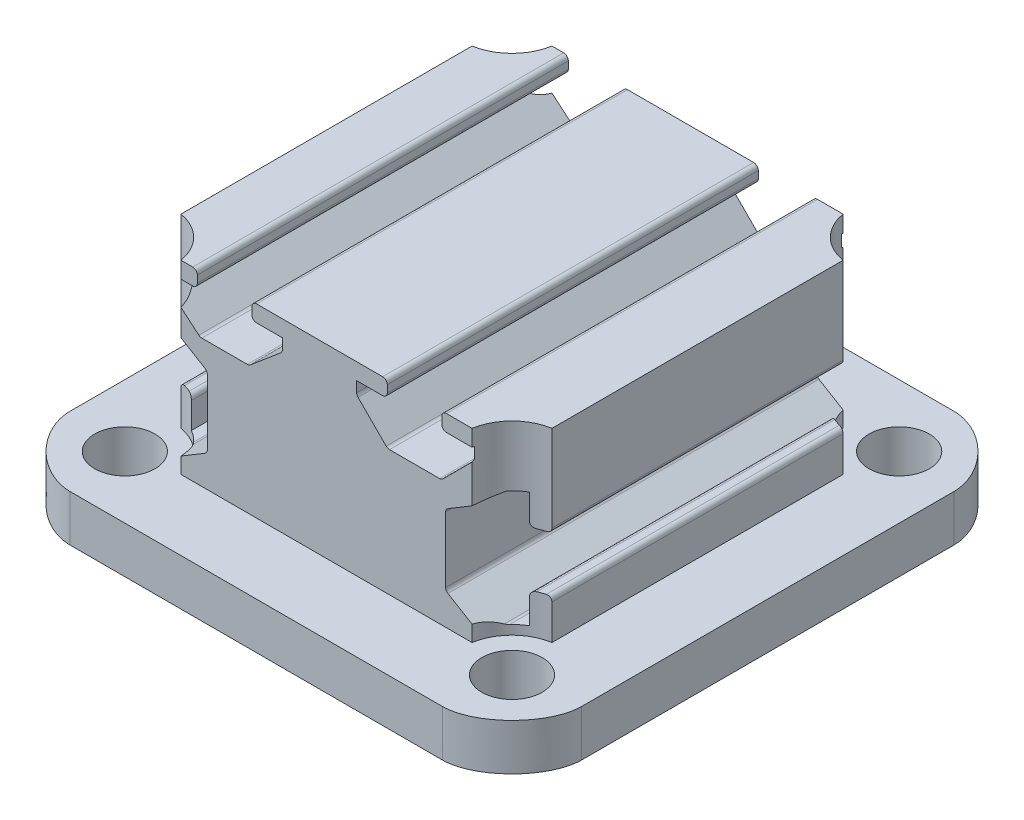
SolidWorks part; units mm, degrees
ref_plane "Front Plane" through (0, 0, 0) normal (0, 0, 1) x (1, 0, 0)
ref_plane "Top Plane" through (0, 0, 0) normal (0, 1, 0) x (1, 0, 0)
ref_plane "Right Plane" through (0, 0, 0) normal (1, 0, 0) x (0, 0, -1)
sketch "Sketch1" plane through (0, 0, 0) normal (0, 1, 0) x (1, 0, 0)
  line L1 (-27.57, -27.57) -> (27.57, -27.57)
  line L2 (-27.57, -27.57) -> (-27.57, 27.57)
  line L3 (-27.57, 27.57) -> (27.57, 27.57)
  line L4 (27.57, -27.57) -> (27.57, 27.57)
  line L5 (-27.57, -27.57) -> (27.57, 27.57) construction
  line L6 (-27.57, 27.57) -> (27.57, -27.57) construction
  point P0 (0, 0)
  dimension "D1" = 55.14
  dimension "D2" = 55.14
extrude "Boss-Extrude1" add sketch "Sketch1" along normal blind 5
sketch "Sketch2" plane through (0, 5, 0) normal (0, 1, 0) x (1, 0, 0)
  line L0 (-27.57, -27.57) -> (27.57, -27.57) construction
  line L1 (27.57, -27.57) -> (27.57, 27.57) construction
  line L2 (-27.57, 27.57) -> (-27.57, -27.57) construction
  line L3 (27.57, 27.57) -> (-27.57, 27.57) construction
  circle A0 centre (20.87, -20.87) radius 3.25
  circle A1 centre (-20.87, -20.87) radius 3.25
  circle A2 centre (-20.87, 20.87) radius 3.25
  circle A3 centre (20.87, 20.87) radius 3.25
  dimension "D2" = 6.5
  dimension "D3" = 6.7
  dimension "D4" = 6.5
  dimension "D5" = 6.7
  dimension "D7" = 6.5
  dimension "D10" = 6.5
  dimension "D12" = 6.7
  dimension "D1" = 6.7
  dimension "D6" = 6.7
  dimension "D8" = 6.7
  dimension "D9" = 6.7
  dimension "D11" = 6.7
extrude "Cut-Extrude1" cut sketch "Sketch2" against normal through all
fillet "Fillet1" radius 7.5 4 edges at (-27.57, 2.5, -27.57) (-27.57, 2.5, 27.57) (27.57, 2.5, 27.57) (27.57, 2.5, -27.57) conic radius 10
sketch "Sketch3" plane through (0, 5, 0) normal (0, 1, 0) x (1, 0, 0)
  line L1 (-20, -20) -> (20, -20)
  line L2 (-20, -20) -> (-20, 20)
  line L3 (-20, 20) -> (20, 20)
  line L4 (20, -20) -> (20, 20)
  line L5 (-20, -20) -> (20, 20) construction
  line L6 (-20, 20) -> (20, -20) construction
  point P0 (0, 0)
  dimension "D1" = 40
  dimension "D2" = 40
extrude "Boss-Extrude2" add sketch "Sketch3" along normal blind 20
extrude "Cut-Extrude2" cut sketch "Sketch2<2>" against normal through all both and the other way through all
sketch "Sketch2<2>" plane through (0, 5, 0) normal (0, 1, 0) x (1, 0, 0) same geometry as "Sketch2"
sketch "Sketch5" plane through (0, 5, 0) normal (0, 1, 0) x (1, 0, 0)
  circle A0 centre (-20.87, 20.87) radius 5.25
  arc A1 (-17.7386, 20) -> (-20, 17.7386) centre (-20.87, 20.87) ccw construction
  circle A2 centre (20.87, 20.87) radius 5.25
  arc A3 (20, 17.7386) -> (17.7386, 20) centre (20.87, 20.87) ccw construction
  circle A4 centre (-20.87, -20.87) radius 5.25
  arc A5 (-20, -17.7386) -> (-17.7386, -20) centre (-20.87, -20.87) ccw construction
  circle A6 centre (20.87, -20.87) radius 5.25
  arc A7 (17.7386, -20) -> (20, -17.7386) centre (20.87, -20.87) ccw construction
  dimension "D1" = 2
  dimension "D2" = 2
  dimension "D3" = 2
  dimension "D4" = 2
extrude "Cut-Extrude3" cut sketch "Sketch5" along normal blind 20
sketch "Sketch8" plane through (0, 0, 20) normal (0, 0, 1) x (1, 0, 0)
  line L0 (-13.9258, 25) -> (-13.9258, 23.23)
  line L1 (-13.9258, 23.23) -> (-17.2258, 23.23)
  line L2 (-17.2258, 23.23) -> (-17.2258, 21.89)
  line L3 (-17.2258, 21.89) -> (-13.6208, 18.8588)
  line L4 (-13.6208, 18.8588) -> (-8.3508, 18.8588)
  line L5 (-8.3508, 18.8588) -> (-4.7458, 21.89)
  line L6 (-4.7458, 21.89) -> (-4.7458, 23.23)
  line L7 (-4.7458, 23.23) -> (-8.0458, 23.23)
  line L8 (-8.0458, 23.23) -> (-8.0458, 25)
  line L9 (-8.0458, 25) -> (-13.9258, 25)
  line L10 (6.5542, 25) -> (6.5542, 23.23)
  line L11 (6.5542, 23.23) -> (3.2542, 23.23)
  line L12 (3.2542, 23.23) -> (3.2542, 21.89)
  line L13 (3.2542, 21.89) -> (6.5847, 18.5595)
  line L14 (6.5847, 18.5595) -> (12.4037, 18.5595)
  line L15 (12.4037, 18.5595) -> (15.7342, 21.89)
  line L16 (15.7342, 21.89) -> (15.7342, 23.23)
  line L17 (15.7342, 23.23) -> (12.4342, 23.23)
  line L18 (12.4342, 23.23) -> (12.4342, 25)
  line L19 (12.4342, 25) -> (6.5542, 25)
  line L20 (-15.6926, 25) -> (15.6926, 25) construction
  dimension "D1" = 0
  dimension "D2" = 0
extrude "Cut-Extrude5" cut sketch "Sketch8" against normal through all
fillet "Fillet5" radius 0.5 16 edges at (15.7342, 21.89, 0) (3.2542, 21.89, 0) (12.4037, 18.5595, 0) (6.5847, 18.5595, 0) (6.5542, 25, 0) (6.5542, 23.23, 0) (12.4342, 23.23, 0) (12.4342, 25, 0) (-8.0458, 25, 0) (-8.0458, 23.23, 0) (-4.7458, 21.89, 0) (-8.3508, 18.8588, 0) (-13.6208, 18.8588, 0) (-17.2258, 21.89, 0) (-13.9258, 23.23, 0) (-13.9258, 25, 0)
ref_plane "Plane1" through (0, 0, -20) normal (0, 0, -1) x (-1, 0, 0)
sketch "Sketch10" plane through (0, 0, -20) normal (0, 0, -1) x (-1, 0, 0)
  line L0 (20, 15.18) -> (18.23, 15.18)
  line L1 (20, 5) -> (20, 25) construction
  line L2 (18.23, 15.18) -> (18.23, 18.48)
  line L3 (18.23, 18.48) -> (16.89, 18.48)
  line L4 (16.89, 18.48) -> (12.8512, 16.0567)
  line L5 (12.8512, 16.0567) -> (12.8512, 8.4233)
  line L6 (12.8512, 8.4233) -> (16.89, 6)
  line L7 (16.89, 6) -> (18.23, 6)
  line L8 (18.23, 6) -> (18.23, 9.3)
  line L9 (18.23, 9.3) -> (20, 9.3)
  line L10 (20, 9.3) -> (20, 15.18)
  line L11 (20, 5) -> (15.6926, 5) construction
  dimension "D1" = 5.88
  dimension "D2" = 1.77
  dimension "D3" = 1.77
  dimension "D4" = 3.3
  dimension "D5" = 3.3
  dimension "D6" = 1.34
  dimension "D7" = 1.34
  dimension "D8" = 4.71
  dimension "D9" = 4.71
  dimension "D10" = 1
extrude "Cut-Extrude6" cut sketch "Sketch10" against normal through all
fillet "Fillet6" radius 0.5 8 edges at (-18.23, 15.18, 0) (-20, 15.18, 0) (-20, 9.3, 0) (-18.23, 9.3, 0) (-16.89, 6, 0) (-16.89, 18.48, 0) (-12.8512, 8.4233, 0) (-12.8512, 16.0567, 0)
sketch "Sketch11" plane through (0, 0, -20) normal (0, 0, -1) x (-1, 0, 0)
  line L0 (-20, 9.3) -> (-18.23, 9.3)
  line L1 (-18.23, 9.3) -> (-18.23, 6)
  line L2 (-18.23, 6) -> (-16.89, 6)
  line L3 (-16.89, 6) -> (-12.8512, 8.4233)
  line L4 (-12.8512, 8.4233) -> (-12.8512, 16.0567)
  line L5 (-12.8512, 16.0567) -> (-16.89, 18.48)
  line L6 (-16.89, 18.48) -> (-18.23, 18.48)
  line L7 (-18.23, 18.48) -> (-18.23, 15.18)
  line L8 (-18.23, 15.18) -> (-20, 15.18)
  line L9 (-20, 15.18) -> (-20, 9.3)
  line L11 (-20.07, 5) -> (20.07, 5) construction
  point P10 (0, 0)
  dimension "D1" = 1
extrude "Cut-Extrude7" cut sketch "Sketch11" against normal through all
fillet "Fillet7" radius 0.5 8 edges at (12.8512, 8.4233, 0) (12.8512, 16.0567, 0) (16.89, 18.48, 0) (16.89, 6, 0) (18.23, 9.3, 0) (20, 9.3, 0) (20, 15.18, 0) (18.23, 15.18, 0)
